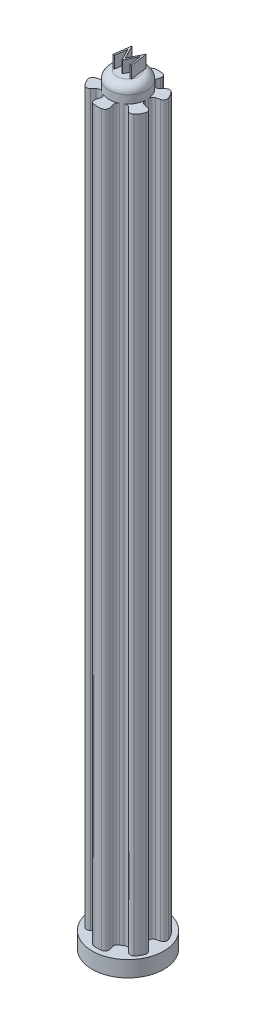
SolidWorks part; units mm, degrees
ref_plane "Front Plane" through (0, 0, 0) normal (0, 0, 1) x (1, 0, 0)
ref_plane "Top Plane" through (0, 0, 0) normal (0, 1, 0) x (1, 0, 0)
ref_plane "Right Plane" through (0, 0, 0) normal (1, 0, 0) x (0, 0, -1)
sketch "Sketch2" plane through (0, 0, 0) normal (0, 1, 0) x (1, 0, 0)
  line L0 (0, 0) -> (0.0739, 0)
  line L2 (2.3008, -0.5891) -> (3.7752, -0.9786)
  line L3 (0.0739, 0) -> (0.1042, -0.0303)
  line L4 (0, 0) -> (0.0858, -0.0446)
  line L5 (1.6802, 1.6786) -> (2.7413, 2.7388)
  line L6 (-1.6794, 1.6794) -> (-2.74, 2.74)
  line L8 (0.6147, 2.2941) -> (1.0029, 3.743)
  line L9 (-0.6147, 2.2941) -> (-1.0029, 3.743)
  line L10 (2.2941, 0.6147) -> (3.743, 1.0029)
  line L11 (0, 0) -> (0.1042, -0.0303)
  line L12 (-2.2941, 0.6147) -> (-3.743, 1.0029)
  line L13 (0.0739, 0) -> (0.0858, -0.0446)
  line L14 (-0.6147, -2.2941) -> (-1.0029, -3.743)
  line L15 (-2.2941, -0.6147) -> (-3.743, -1.0029)
  line L16 (-1.6794, -1.6794) -> (-2.74, -2.74)
  line L17 (0.6814, -2.2752) -> (1.0684, -3.7248)
  line L18 (1.7145, -1.6435) -> (2.7672, -2.6981)
  arc A0 (-2.2941, 0.6147) -> (-2.2941, -0.6147) centre (0, 0) ccw
  arc A1 (-2.74, 2.74) -> (-3.743, 1.0029) centre (0, 0) ccw
  arc A2 (1.0029, 3.743) -> (-1.0029, 3.743) centre (0, 0) ccw
  arc A3 (3.743, 1.0029) -> (2.7413, 2.7388) centre (0, 0) ccw
  arc A5 (-1.0029, -3.743) -> (1.0684, -3.7248) centre (0, 0) ccw
  arc A6 (-3.743, -1.0029) -> (-2.74, -2.74) centre (0, 0) ccw
  arc A7 (-2.74, 2.74) -> (-3.743, 1.0029) centre (0, 0) ccw
  arc A8 (1.0029, 3.743) -> (-1.0029, 3.743) centre (0, 0) ccw
  arc A9 (3.743, 1.0029) -> (2.7413, 2.7388) centre (0, 0) ccw
  arc A10 (-3.743, -1.0029) -> (-2.74, -2.74) centre (0, 0) ccw
  arc A11 (-1.0029, -3.743) -> (1.0684, -3.7248) centre (0, 0) ccw
  arc A12 (2.7672, -2.6981) -> (3.7752, -0.9786) centre (1.7753, -0.9614) ccw
  arc A13 (-0.6147, 2.2941) -> (-1.6794, 1.6794) centre (0, 0) ccw
  arc A14 (1.6802, 1.6786) -> (0.6147, 2.2941) centre (0, 0) ccw
  arc A15 (2.3008, -0.5891) -> (2.2941, 0.6147) centre (0, 0) ccw
  arc A16 (0.6814, -2.2752) -> (1.7145, -1.6435) centre (0, 0) ccw
  arc A17 (-1.6794, -1.6794) -> (-0.6147, -2.2941) centre (0, 0) ccw
  dimension "D1" = 3.875
  dimension "D2" = 2.375
extrude "Boss-Extrude1" add sketch "Sketch2" along normal blind 91.5 contours L16 A17 L14 A5 L17 A16 L18 A12 L2 A15 L10 A3 L5 A14 L8 A2 L9 A13 L6 A1 L12 A0 L15 A6 L11 L13 L4 L0 L3 region at (0.0225, 0, 0.0171)
sketch "Sketch3" plane through (0, 0, 0) normal (0, -1, 0) x (1, 0, 0)
  circle A0 centre (0, 0) radius 4.5
  dimension "D1" = 9
extrude "Boss-Extrude2" add sketch "Sketch3" along normal blind 2
sketch "Sketch4" plane through (0, 91.5, 0) normal (0, 1, 0) x (1, 0, 0)
  circle A0 centre (0, 0) radius 2.375
  dimension "D1" = 4.75
extrude "Boss-Extrude3" add sketch "Sketch4" along normal blind 2
fillet "Fillet1" radius 0.5 24 edges at (-2.74, 45.75, -2.74) (-1.6794, 45.75, -1.6794) (-0.6147, 45.75, -2.2941) (-1.0029, 45.75, -3.743) (1.0029, 45.75, -3.743) (0.6147, 45.75, -2.2941) (1.6802, 45.75, -1.6786) (2.7413, 45.75, -2.7388) (3.743, 45.75, -1.0029) (2.2941, 45.75, -0.6147) (2.3008, 45.75, 0.5891) (3.7752, 45.75, 0.9786) (2.7672, 45.75, 2.6981) (1.7145, 45.75, 1.6435) (0.6814, 45.75, 2.2752) (-1.6794, 45.75, 1.6794) (-2.2941, 45.75, 0.6147) (-2.2941, 45.75, -0.6147) (-0.6147, 45.75, 2.2941) (-3.743, 45.75, -1.0029) (-3.743, 45.75, 1.0029) (-2.74, 45.75, 2.74) (-1.0029, 45.75, 3.743) (1.0684, 45.75, 3.7248)
sketch "Sketch5" plane through (0, 93.5, 0) normal (0, 1, 0) x (1, 0, 0)
  text T0 "M" font "Century Gothic" height in points 8
sketch "Sketch6" plane through (0, -2, 0) normal (0, -1, 0) x (1, 0, 0)
  circle A0 centre (0, 0) radius 1
  dimension "D1" = 2
extrude "Cut-Extrude4" cut sketch "Sketch6" against normal blind 0.5 draft 50
extrude "Boss-Extrude4" add sketch "Sketch5" along normal blind 1.5
fillet "Fillet2" radius 1 1 edges at (0, 93.5, 2.375)
